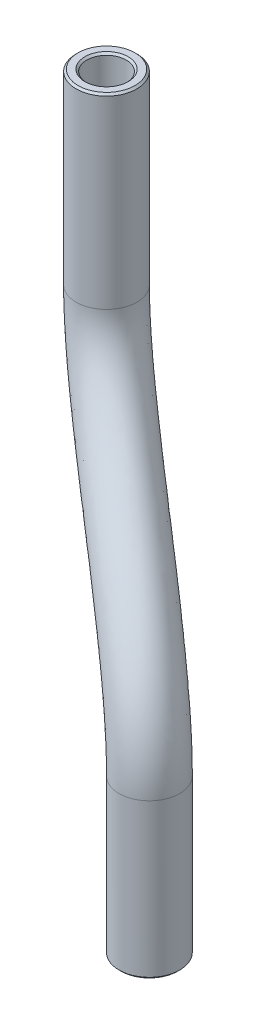
SolidWorks part; units mm, degrees
ref_plane "Front Plane" through (0, 0, 0) normal (0, 0, 1) x (1, 0, 0)
ref_plane "Top Plane" through (0, 0, 0) normal (0, 1, 0) x (1, 0, 0)
ref_plane "Right Plane" through (0, 0, 0) normal (1, 0, 0) x (0, 0, -1)
sketch3d "3DSketch1"
  line L0 (83.325, -74.325, 25.85) -> (83.325, -62.025, 25.85)
  line L1 (93.825, -93.2823, 33.525) -> (93.825, -103.4823, 33.525)
  spline S0 degree 3 poles (83.325, -74.325, 25.85) (83.325, -77.9144, 25.85) (88.575, -83.609, 29.6875) (93.825, -89.1004, 33.525) (93.825, -93.2823, 33.525) knots 0 0 0 0 0.468393 1 1 1 1
sketch "Sketch1" plane through (0, -95.3823, 0) normal (0, 1, 0) x (1, 0, 0)
  circle A0 centre (93.825, -33.525) radius 1.3
  circle A1 centre (93.825, -33.525) radius 2
  circle A2 centre (93.825, -33.525) radius 3.5 construction
  dimension "D1" = 4
  dimension "D2" = 2.6
sweep "Sweep1" add profiles "Sketch1" path "3DSketch1"
chamfer "Chamfer1" distance 0.127 angle 45 4 edges at (91.825, -103.4823, 33.525) (92.525, -103.4823, 33.525) (81.325, -62.025, 25.85) (82.025, -62.025, 25.85)
